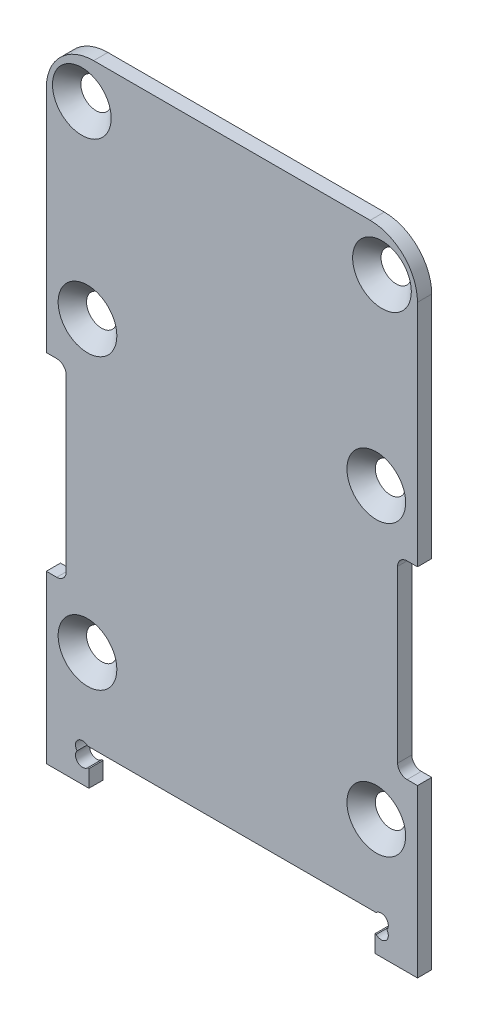
SolidWorks part; units mm, degrees
ref_plane "Front Plane" through (0, 0, 0) normal (0, 0, 1) x (1, 0, 0)
ref_plane "Top Plane" through (0, 0, 0) normal (0, 1, 0) x (1, 0, 0)
ref_plane "Right Plane" through (0, 0, 0) normal (1, 0, 0) x (0, 0, -1)
sketch "Sketch1" plane through (0, 0, 0) normal (0, 0, 1) x (1, 0, 0)
  line L1 (-19.6, 39.2) -> (19.6, 39.2)
  line L2 (-19.6, 39.2) -> (-19.6, -27.6)
  line L3 (19.6, -27.6) -> (15.1, -27.6) construction
  line L4 (19.6, 39.2) -> (19.6, -27.6)
  line L5 (-7.95, 39.2) -> (-14.6, 39.2) construction
  line L6 (-19.6, -10) -> (-19.6, 10) construction
  line L7 (19.6, 10) -> (19.6, -10) construction
  line L9 (15.1, -27.6) -> (15.1, -25.8) construction
  line L10 (15.1, -25.8) -> (16.3, -25.8) construction
  line L11 (16.3, -23.8) -> (16.3, -25.8) construction
  line L14 (-16.3, -23.8) -> (-3.35, -23.8) construction
  line L15 (-16.3, -23.8) -> (-16.3, -25.8) construction
  line L16 (-15.1, -27.6) -> (-15.1, -25.8) construction
  line L17 (-15.1, -27.6) -> (-19.6, -27.6) construction
  line L19 (19.6, -27.6) -> (15.1, -27.6)
  line L20 (15.1, -27.6) -> (15.1, -25.8)
  line L21 (15.1, -25.8) -> (16.3, -25.8)
  line L22 (16.3, -23.8) -> (16.3, -25.8)
  line L24 (-16.3, -25.8) -> (-15.1, -25.8) construction
  line L25 (-16.3, -23.8) -> (16.3, -23.8)
  line L26 (-16.3, -23.8) -> (-16.3, -25.8)
  line L27 (-15.1, -27.6) -> (-15.1, -25.8)
  line L28 (-15.1, -27.6) -> (-19.6, -27.6)
  line L29 (-16.3, -25.8) -> (-15.1, -25.8)
  point P8 (0, 0)
  point P9 (1.8429, -23.8)
  point P10 (16.0668, -23.8)
extrude "Base" add sketch "Sketch1" along normal blind 1.5 contours L21 L4 L1 L2 region at (0, 7.3053, 0)
sketch "Sketch2" plane through (0, 0, 1.5) normal (0, 0, 1) x (1, 0, 0)
  line L0 (0, 34.85) -> (0, -15.25) construction
  line L1 (15.25, 34.85) -> (-15.25, 34.85) construction
  line L2 (15.25, -15.25) -> (-15.25, -15.25) construction
  line L3 (-15.25, 0) -> (15.25, 0) construction
  line L4 (-15.25, -15.25) -> (-15.25, 34.85) construction
  line L5 (15.25, -15.25) -> (15.25, 34.85) construction
  circle A0 centre (-15.25, 15.25) radius 1.6
  circle A1 centre (-15.85, 34.85) radius 1.6
  circle A2 centre (15.85, 34.85) radius 1.6
  circle A3 centre (15.25, 15.25) radius 1.6
  circle A4 centre (15.25, -15.25) radius 1.6
  circle A5 centre (-15.25, -15.25) radius 1.6
  circle A6 centre (-15.85, 34.85) radius 1.6 construction
  circle A7 centre (15.85, 34.85) radius 1.6 construction
  dimension "D1" = 3.2
sketch "Sketch3" plane through (0, 0, 1.5) normal (0, 0, 1) x (1, 0, 0)
  line L0 (-17.5, 42.8) -> (-17.5, -31.2) construction
  line L1 (-17.5, -10) -> (-19.6, -10)
  line L2 (-17.5, -10) -> (-17.5, 10)
  line L3 (-17.5, 10) -> (-19.6, 10)
  line L4 (-19.6, -10) -> (-19.6, 10)
  line L5 (-17.5, -10) -> (-19.6, 10) construction
  line L6 (-17.5, 10) -> (-19.6, -10) construction
  line L7 (-19.6, 39.2) -> (-19.6, -27.6) construction
  line L8 (0, 0) -> (-19.6, 0) construction
  point P4 (-18.55, 0)
extrude "Battery strap cut" cut sketch "Sketch3" against normal up to next
fillet "Battery strap fillet" radius 1 2 edges at (-17.5, -10, 0.75) (-17.5, 10, 0.75)
mirror "Battery strap other side" about plane through (0, 0, 0) normal (1, 0, 0) of "Battery strap cut", "Battery strap fillet"
fillet "Fillet2" radius 5 2 edges at (-19.6, 39.2, 0.75) (19.6, 39.2, 0.75)
extrude "Hole cut" cut sketch "Sketch2" against normal up to next
chamfer "Bolt head chamber" distance 1.5 angle 45 6 edges at (-13.65, 15.25, 1.5) (-16.85, -15.25, 1.5) (16.85, -15.25, 1.5) (-14.25, 34.85, 1.5) (17.45, 34.85, 1.5) (13.65, 15.25, 1.5)
sketch "Sketch4" plane through (0, 0, 1.5) normal (0, 0, 1) x (1, 0, 0)
  line L0 (-15.7697, -24.3303) -> (-16.3, -23.8) construction
  line L2 (-16.3, -24.8) -> (-15.1139, -24.8) construction
  line L3 (0, -23.8) -> (0, -26.7588) construction
  line L5 (-16.3, -23.8) -> (-16.3, -25.8) construction
  circle A0 centre (-15.7697, -24.3303) radius 0.75
  circle A1 centre (-15.7697, -25.2697) radius 0.75
  circle A2 centre (15.7697, -25.2697) radius 0.75
  circle A3 centre (15.7697, -24.3303) radius 0.75
  point P19 (0, 0)
  dimension "D2" = 1.5
  dimension "D1" = 45
extrude "Milling holes" cut sketch "Sketch4" against normal blind 10 contours A0 | A1 | A2 | A3
